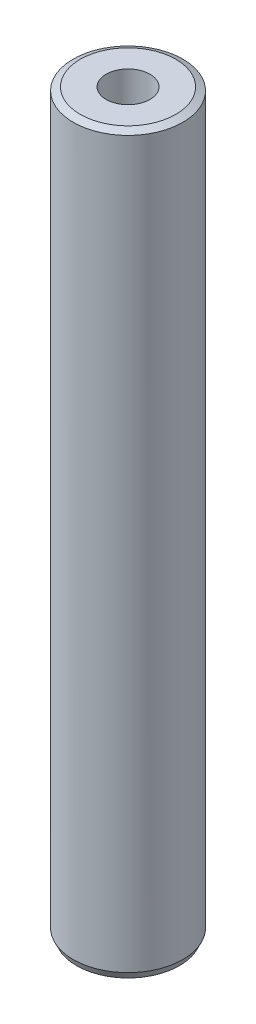
SolidWorks part; units mm, degrees
ref_plane "Front Plane" through (0, 0, 0) normal (0, 0, 1) x (1, 0, 0)
ref_plane "Top Plane" through (0, 0, 0) normal (0, 1, 0) x (1, 0, 0)
ref_plane "Right Plane" through (0, 0, 0) normal (1, 0, 0) x (0, 0, -1)
sketch "Sketch1" plane through (0, 0, 0) normal (0, 1, 0) x (1, 0, 0)
  circle A0 centre (0, 0) radius 22.5
  dimension "SHAFT_OD" = 45
extrude "Boss-Extrude1" add sketch "Sketch1" along normal blind 301.9023
sketch "Sketch2" plane through (0, 0, 0) normal (0, 1, 0) x (1, 0, 0)
  circle A0 centre (0, 0) radius 9.004
  dimension "BORE_D" = 18.008
extrude "Cut-Extrude1" cut sketch "Sketch2" along normal through all
chamfer "Chamfer1" distance 1.3811 angle 64.417 2 edges at (0, 301.9023, 22.5) (0, 0, 22.5) first distance on face at (0, 301.9023, 22.5) first distance on face at (0, 0, 9.004)
